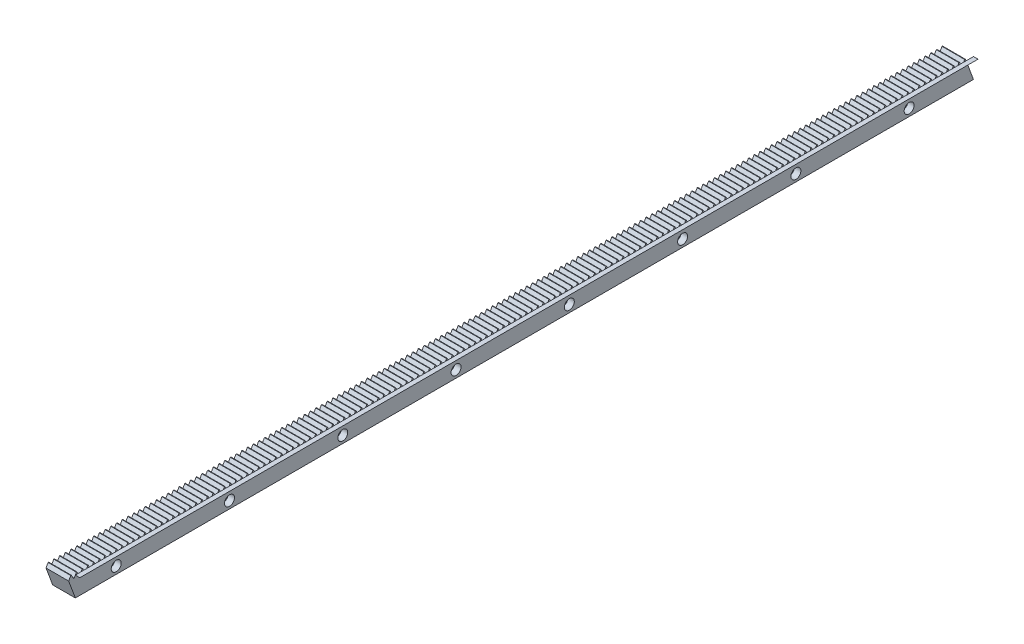
SolidWorks part; units mm, degrees
material "45#"
ref_plane "前视" through (0, 0, 0) normal (0, 0, 1) x (1, 0, 0)
ref_plane "上视" through (0, 0, 0) normal (0, 1, 0) x (1, 0, 0)
ref_plane "右视" through (0, 0, 0) normal (1, 0, 0) x (0, 0, -1)
sketch "草图1" plane through (0, 0, 0) normal (1, 0, 0) x (0, 0, -1)
  line L0 (-1000, 0) -> (0, 0)
  line L1 (0, 0) -> (0, 24)
  line L2 (0, 24) -> (-1000, 24)
  line L3 (-1000, 24) -> (-1000, 0)
  dimension "D1" = 24
  dimension "D2" = 1000
extrude "凸台-拉伸1" add sketch "草图1" against normal mid plane 25
sketch "草图2" plane through (0, 0, 0) normal (1, 0, 0) x (0, 0, -1)
  line L0 (-2.8273, 26) -> (-2.8273, 24)
  line L1 (-2.8273, 24) -> (-0.3142, 19.5)
  line L2 (-0.3142, 19.5) -> (0.3142, 19.5)
  line L3 (0.3142, 19.5) -> (2.8274, 24)
  line L4 (2.8274, 24) -> (2.8274, 26)
  line L5 (2.8274, 26) -> (-2.8273, 26)
  line L6 (0, 24) -> (0, 17.5972) construction
  line L7 (0, 0) -> (0, 24) construction
  line L9 (0, 24) -> (-1000, 24) construction
  dimension "D1" = 5.6547
  dimension "D2" = 6.5
  dimension "D3" = 4.5
  dimension "D4" = 0.6283
extrude "切除-拉伸1" cut sketch "草图2" along normal through all and the other way through all
pattern_linear "阵列(线性)3" count 160 spacing 6.283 along (0, 0, 1) of "切除-拉伸1"
sketch "草图6" plane through (12.5, 0, 0) normal (1, 0, 0) x (0, 0, -1)
  line L0 (-1000, 24) -> (-991.1, 0)
  line L1 (-991.1, 0) -> (-1000, 0)
  line L2 (-1000, 0) -> (-1000, 24)
  line L3 (-995.5414, 24) -> (-996.1697, 24) construction
  line L4 (0, 24) -> (-8.9, 24)
  line L5 (-1000, 0) -> (0, 0) construction
  line L6 (-8.9, 24) -> (0, 0)
  line L7 (0, 0) -> (0, 24)
  line L10 (-2.8273, 24) -> (-3.4556, 24) construction
  dimension "D1" = 8.9
extrude "切除-拉伸2" cut sketch "草图6" against normal through all
hole_wizard "打孔尺寸根据内六角圆柱头螺钉的类型1" positions "草图4" profile "草图3" counterbore size "M6" standard "Gb" end condition through all
sketch "草图4" plane through (12.5, 0, 0) normal (1, 0, 0) x (0, 0, -1)
  line L1 (-991.1, 0) -> (0, 0) construction
  point P3 (-70.9843, 8)
  dimension "D1" = 62.5
  dimension "D2" = 8
sketch "草图3" plane through (12.5, 8, 70.9843) normal (0, 1, 0) x (0, 0, -1)
  line L0 (0, 0) -> (0, 25)
  line L1 (0, 25) -> (3.5, 25)
  line L3 (3.5, 25) -> (3.5, 7)
  line L4 (3.5, 7) -> (5.5, 7)
  line L5 (5.5, 7) -> (5.5, 0)
  line L7 (5.5, 0) -> (0, 0)
  line L11 (0, -6.35) -> (0, 107.95) construction
  dimension "通孔孔直径" = 7
  dimension "通孔孔深度" = 25
  dimension "柱形沉头孔直径" = 11
  dimension "柱形沉头孔深度" = 7
pattern_linear "阵列(线性)4" count 8 spacing 125 along (0, 0, 1) of "打孔尺寸根据内六角圆柱头螺钉的类型1"
sketch "草图5" plane through (12.5, 0, 0) normal (1, 0, 0) x (0, 0, -1)
  line L0 (-991.1, 21.88) -> (0, 21.88)
  dimension "D1" = 2.12
surface "曲面-拉伸1" sketch "草图5" parameters "D1"=5
